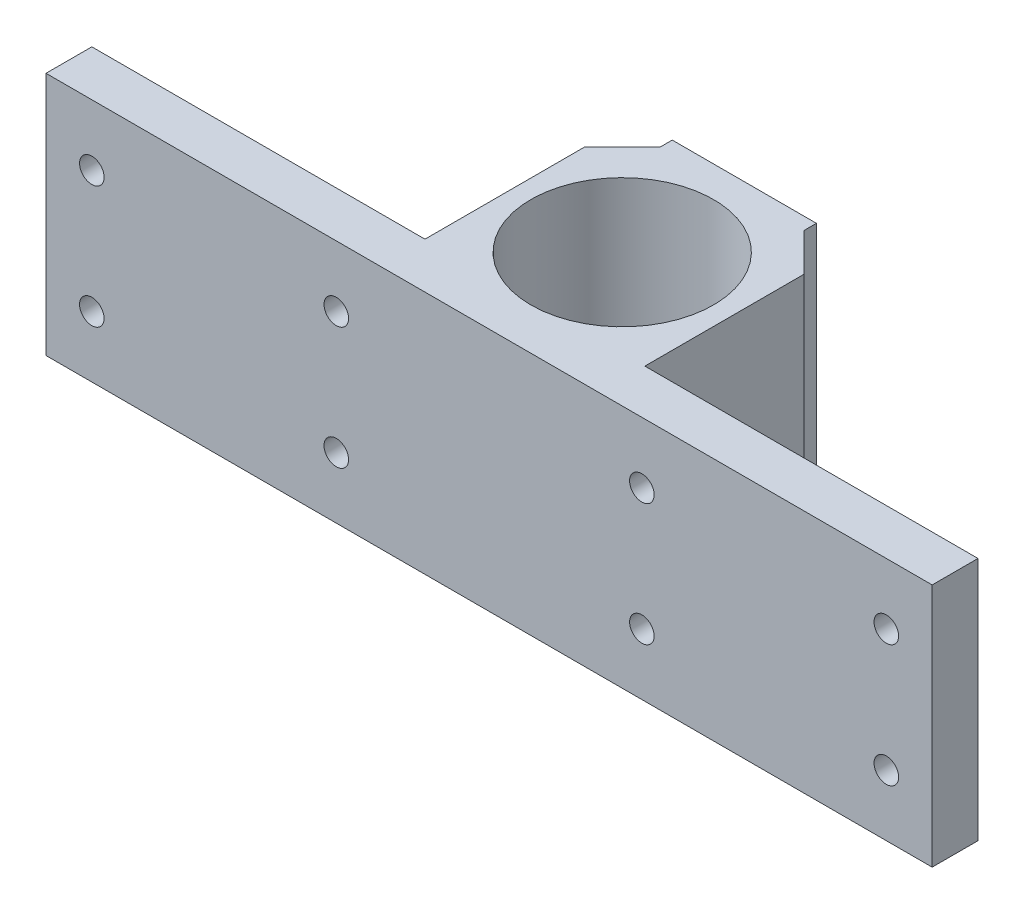
SolidWorks part; units mm, degrees
ref_plane "Front Plane" through (0, 0, 0) normal (0, 0, 1) x (1, 0, 0)
ref_plane "Top Plane" through (0, 0, 0) normal (0, 1, 0) x (1, 0, 0)
ref_plane "Right Plane" through (0, 0, 0) normal (1, 0, 0) x (0, 0, -1)
sketch "Sketch1" plane through (0, 0, 0) normal (0, 0, 1) x (1, 0, 0)
  line L1 (-87.7906, 21.747) -> (96.3594, 21.747)
  line L2 (-87.7906, 21.747) -> (-87.7906, -29.053)
  line L3 (-87.7906, -29.053) -> (96.3594, -29.053)
  line L4 (96.3594, 21.747) -> (96.3594, -29.053)
  dimension "D1" = 184.15
  dimension "D2" = 50.8
extrude "Boss-Extrude1" add sketch "Sketch1" along normal blind 9.525
sketch "Sketch5" plane through (0, 21.747, 0) normal (0, 1, 0) x (1, 0, 0)
  line L0 (10.8884, 0) -> (10.8884, -9.525)
  line L1 (96.3594, 0) -> (-87.7906, 0) construction
  line L2 (96.3594, -9.525) -> (-87.7906, -9.525) construction
  line L3 (-2.3196, 0) -> (-2.3196, -9.525)
  point P8 (4.2844, 0)
  dimension "D1" = 6.604
  dimension "D2" = 6.604
sketch "Sketch6" plane through (0, 21.747, 0) normal (0, 1, 0) x (1, 0, 0)
  arc A0 (10.8884, 0) -> (-2.3196, 0) centre (4.2844, 10.8827) cw
extrude "Cut-Extrude1" cut sketch "Sketch6" against normal through all and the other way through all flip side to cut
sketch "Sketch7" plane through (0, 21.747, 0) normal (0, 1, 0) x (1, 0, 0)
  line L0 (4.2844, -4.7215) -> (4.2844, 18.1385)
  line L1 (-87.7906, -9.525) -> (-87.7906, 0) construction
  circle A1 centre (4.2844, 18.1385) radius 22.8473
  dimension "D1" = 22.86
  dimension "D2" = 92.075
extrude "Boss-Extrude2" add sketch "Sketch7" against normal through all contours A1
sketch "Sketch8" plane through (0, 21.747, 0) normal (0, 1, 0) x (1, 0, 0)
  circle A0 centre (4.2844, 18.1385) radius 18.9865
  dimension "D1" = 37.973
extrude "Cut-Extrude2" cut sketch "Sketch8" against normal blind 45.72
sketch "Sketch9" plane through (0, -23.973, 0) normal (0, 1, 0) x (1, 0, 0)
  circle A0 centre (4.2844, 18.1385) radius 7.9375
  circle A1 centre (4.2844, 18.1385) radius 18.9865 construction
  dimension "D1" = 15.875
  dimension "D2" = 0
extrude "Cut-Extrude3" cut sketch "Sketch9" against normal through all
sketch "Sketch12" plane through (0, 21.747, 0) normal (0, 1, 0) x (1, 0, 0)
  line L0 (27.1317, 18.1385) -> (27.1317, 0)
  line L1 (96.3594, 0) -> (18.1766, 0) construction
  line L2 (27.1317, 0) -> (18.1766, 0)
  line L3 (-18.5629, 18.1385) -> (-18.5629, 0)
  line L4 (-9.6078, 0) -> (-87.7906, 0) construction
  line L5 (-18.5629, 0) -> (-9.6078, 0)
  circle A0 centre (4.2844, 18.1385) radius 22.8473 construction
  arc A1 (18.1766, 0) -> (27.1317, 18.1385) centre (4.2844, 18.1385) ccw
  arc A2 (-9.6078, 0) -> (-18.5629, 18.1385) centre (4.2844, 18.1385) cw
extrude "Boss-Extrude3" add sketch "Sketch12" against normal up to surface (50.8 mm away) up to face at (4.2844, -29.053, -10.201)
sketch "Sketch16" plane through (0, -29.053, 0) normal (0, -1, 0) x (1, 0, 0)
  line L0 (-18.5629, -18.1385) -> (-18.5629, -40.9857)
  line L1 (4.2844, -40.9857) -> (-18.5629, -40.9857)
  arc A0 (-18.5629, -18.1385) -> (27.1317, -18.1385) centre (4.2844, -18.1385) ccw construction
  arc A1 (-18.5629, -18.1385) -> (4.2844, -40.9857) centre (4.2844, -18.1385) ccw
extrude "Boss-Extrude4" add sketch "Sketch16" against normal up to surface (50.8 mm away) up to face at (4.2844, 21.747, -5.0093)
sketch "Sketch18" plane through (0, -29.053, 0) normal (0, -1, 0) x (1, 0, 0)
  line L0 (27.1317, -18.1385) -> (27.1317, -40.9857)
  line L1 (27.1317, -40.9857) -> (4.2844, -40.9857)
  arc A0 (27.1317, -18.1385) -> (4.2844, -40.9857) centre (4.2844, -18.1385) cw
extrude "Boss-Extrude5" add sketch "Sketch18" against normal up to surface (50.8 mm away) up to face at (4.8102, 21.747, -9.5324)
sketch "Sketch19" plane through (0, 21.747, 0) normal (0, 1, 0) x (1, 0, 0)
  line L2 (27.1317, 40.9857) -> (-18.5629, 40.9857) construction
  line L3 (19.2577, 40.9857) -> (27.1317, 40.9857)
  line L6 (-18.5629, 40.9857) -> (-18.5629, 0) construction
  line L8 (-18.5629, 40.9857) -> (-18.5629, 33.1259)
  line L9 (-18.5629, 33.1259) -> (-10.703, 40.9857)
  line L10 (-10.703, 40.9857) -> (-18.5629, 40.9857)
  line L11 (19.2577, 40.9857) -> (27.1317, 33.1117)
  line L12 (27.1317, 0) -> (27.1317, 40.9857) construction
  line L13 (27.1317, 33.1117) -> (27.1317, 40.9857)
  dimension "D1" = 7.8599
  dimension "D2" = 7.874
extrude "Cut-Extrude6" cut sketch "Sketch19" against normal through all
hole_wizard "#10 Clearance Hole1" positions "Sketch23" profile "Sketch24" hole size "#10" standard "ANSI Inch" end condition through all
sketch "Sketch23" plane through (0, 0, 0) normal (0, 0, -1) x (-1, 0, 0)
  line L0 (87.7906, 21.747) -> (87.7906, -29.053) construction
  line L1 (87.7906, -29.053) -> (18.5629, -29.053) construction
  line L2 (18.5629, 21.747) -> (87.7906, 21.747) construction
  line L3 (-96.3594, -29.053) -> (-96.3594, 21.747) construction
  line L4 (-96.3594, 21.747) -> (-27.1317, 21.747) construction
  line L5 (-27.1317, -29.053) -> (-96.3594, -29.053) construction
  point P0 (78.2656, 9.047)
  point P2 (78.2656, -16.353)
  point P4 (-86.8344, -16.353)
  point P6 (-86.8344, 9.047)
  dimension "D1" = 9.525
  dimension "D2" = 12.7
  dimension "D3" = 12.7
  dimension "D4" = 9.525
  dimension "D5" = 9.525
  dimension "D6" = 12.7
  dimension "D7" = 12.7
  dimension "D8" = 9.525
sketch "Sketch24" plane through (-78.2656, 9.047, 0) normal (1, 0, 0) x (0, 1, 0)
  line L0 (0, 0) -> (0, 9.525)
  line L1 (0, 9.525) -> (2.5527, 9.525)
  line L2 (2.5527, 9.525) -> (2.5527, 0)
  line L5 (2.5527, 0) -> (0, 0)
  line L11 (0, -6.35) -> (0, 107.95) construction
  dimension "Thru Hole Dia." = 5.1054
  dimension "Thru Hole Depth" = 9.525
hole_wizard "#10 Clearance Hole2" positions "Sketch25" profile "Sketch26" hole size "#10" standard "ANSI Inch" end condition through all
sketch "Sketch25" plane through (0, 0, 0) normal (0, 0, -1) x (-1, 0, 0)
  line L0 (87.7906, -29.053) -> (18.5629, -29.053) construction
  line L2 (18.5629, 21.747) -> (87.7906, 21.747) construction
  line L3 (-96.3594, 21.747) -> (-27.1317, 21.747) construction
  line L5 (-27.1317, -29.053) -> (-96.3594, -29.053) construction
  circle A0 centre (78.2656, -16.353) radius 2.5527 construction
  circle A1 centre (78.2656, 9.047) radius 2.5527 construction
  circle A2 centre (-86.8344, 9.047) radius 2.5527 construction
  circle A3 centre (-86.8344, -16.353) radius 2.5527 construction
  point P0 (27.4656, -16.353)
  point P2 (27.4656, 9.047)
  point P4 (-36.0344, 9.047)
  point P6 (-36.0344, -16.353)
  dimension "D1" = 12.7
  dimension "D2" = 50.8
  dimension "D3" = 50.8
  dimension "D4" = 12.7
  dimension "D5" = 12.7
  dimension "D6" = 50.8
  dimension "D7" = 50.8
  dimension "D8" = 12.7
sketch "Sketch26" plane through (-27.4656, -16.353, 0) normal (1, 0, 0) x (0, 1, 0)
  line L0 (0, 0) -> (0, 9.525)
  line L1 (0, 9.525) -> (2.5527, 9.525)
  line L2 (2.5527, 9.525) -> (2.5527, 0)
  line L5 (2.5527, 0) -> (0, 0)
  line L11 (0, -6.35) -> (0, 107.95) construction
  dimension "Thru Hole Dia." = 5.1054
  dimension "Thru Hole Depth" = 9.525
sketch "Sketch31" plane through (0, 0, -40.9857) normal (0, 0, -1) x (-1, 0, 0)
  line L1 (-19.2577, -29.053) -> (10.703, -29.053)
  line L2 (-19.2577, -29.053) -> (-19.2577, 21.747)
  line L3 (-19.2577, 21.747) -> (10.703, 21.747)
  line L4 (10.703, -29.053) -> (10.703, 21.747)
extrude "Boss-Extrude6" add sketch "Sketch31" along normal blind 2.54
hole_wizard "3/16 (0.1875) Diameter Hole3" positions "Sketch32" profile "Sketch33" hole size "3/16" standard "ANSI Inch" end condition up to next
sketch "Sketch32" plane through (-25.8444, 0, -25.8444) normal (-0.7071, 0, -0.7071) x (-0.7071, 0, 0.7071)
  line L0 (-10.2976, -29.053) -> (-21.4131, -29.053) construction
  line L1 (-10.2976, -29.053) -> (-10.2976, 21.747) construction
  point P0 (-15.3776, -20.163)
  point P2 (-15.3776, -7.463)
  dimension "D1" = 8.89
  dimension "D2" = 12.7
  dimension "D3" = 5.08
sketch "Sketch33" plane through (-14.9708, -20.163, -36.718) normal (0, 1, 0) x (-0.7071, 0, 0.7071)
  line L0 (0, 0) -> (0, 7.7726)
  line L1 (0, 7.7726) -> (2.3812, 7.7726)
  line L2 (2.3812, 7.7726) -> (2.3812, 0)
  line L5 (2.3812, 0) -> (0, 0)
  line L11 (0, -6.35) -> (0, 107.95) construction
  dimension "Thru Hole Dia." = 4.7625
  dimension "Thru Hole Depth" = 7.7726
hole_wizard "3/16 (0.1875) Diameter Hole4" positions "Sketch34" profile "Sketch35" hole size "3/16" standard "ANSI Inch" end condition up to next
sketch "Sketch34" plane through (30.1217, 0, -30.1217) normal (0.7071, 0, -0.7071) x (-0.7071, 0, -0.7071)
  line L0 (15.3641, -29.053) -> (4.2285, -29.053) construction
  line L1 (4.2285, -29.053) -> (4.2285, 21.747) construction
  point P0 (9.3085, -20.163)
  point P2 (9.3085, -7.463)
  dimension "D1" = 8.89
  dimension "D2" = 12.7
  dimension "D3" = 5.08
sketch "Sketch35" plane through (23.5395, -20.163, -36.7038) normal (0, 1, 0) x (-0.7071, 0, -0.7071)
  line L0 (0, 0) -> (0, 7.7629)
  line L1 (0, 7.7629) -> (2.3812, 7.7629)
  line L2 (2.3812, 7.7629) -> (2.3812, 0)
  line L5 (2.3812, 0) -> (0, 0)
  line L11 (0, -6.35) -> (0, 107.95) construction
  dimension "Thru Hole Dia." = 4.7625
  dimension "Thru Hole Depth" = 7.7629
